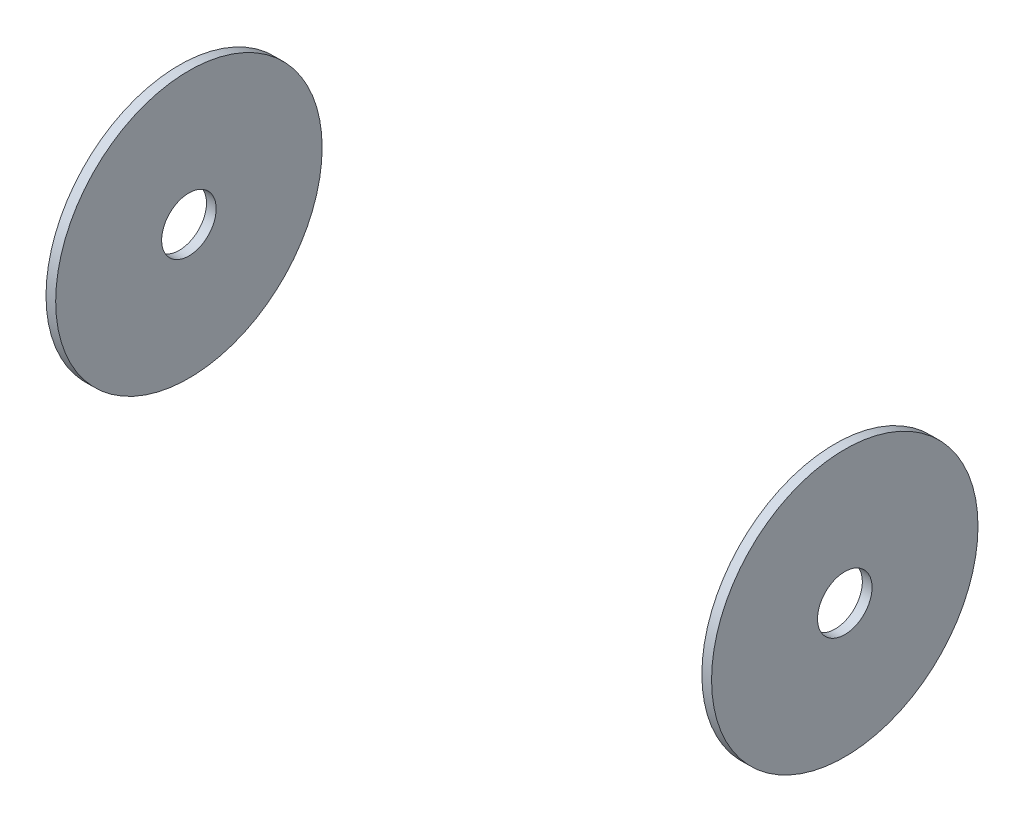
SolidWorks part; units mm, degrees
material "Titanium"
ref_plane "Front Plane" through (0, 0, 0) normal (0, 0, 1) x (1, 0, 0)
ref_plane "Top Plane" through (0, 0, 0) normal (0, 1, 0) x (1, 0, 0)
ref_plane "Right Plane" through (0, 0, 0) normal (1, 0, 0) x (0, 0, -1)
sketch "Sketch1" plane through (50.05, 0, 0) normal (1, 0, 0) x (0, 0, -1)
  circle A0 centre (-177.8, 26.9875) radius 20.6375
  arc A1 (-196.4827, 35.7546) -> (-195.4467, 16.287) centre (-177.8, 26.9875) ccw construction
  circle A2 centre (-177.8, 26.9875) radius 4.2227
  dimension "D1" = 8.4455
extrude "Boss-Extrude1" add sketch "Sketch1" along normal blind 1.5
mirror "Mirror2" about plane through (0, 0, 0) normal (1, 0, 0) of bodies 101
equation "\"weapon shaft threads\"= 5 / 16"
equation "\"D1@Sketch1\"=\"weapon shaft threads\" + .02in"
equation "\"D1@Boss-Extrude1\"=1.5mm"
